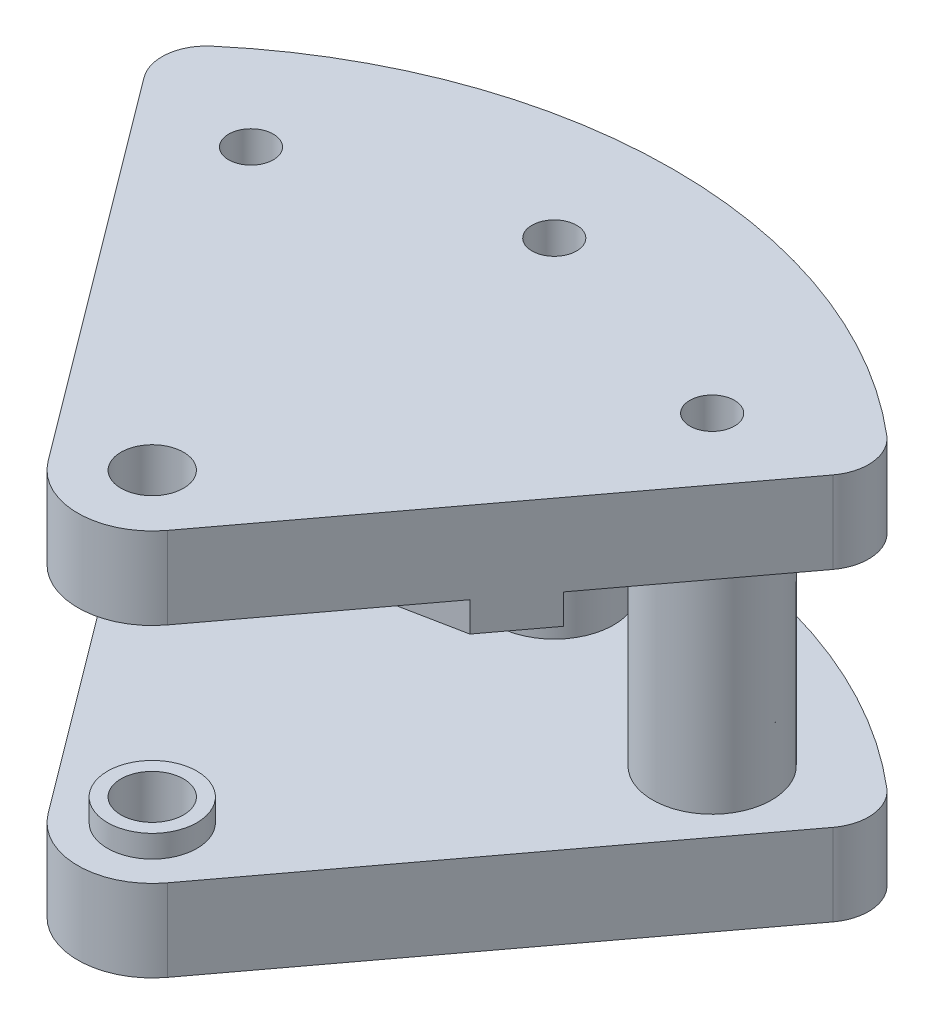
SolidWorks part; units mm, degrees
ref_plane "正面" through (0, 0, 0) normal (0, 0, 1) x (1, 0, 0)
ref_plane "平面" through (0, 0, 0) normal (0, 1, 0) x (1, 0, 0)
ref_plane "右側面" through (0, 0, 0) normal (1, 0, 0) x (0, 0, -1)
sketch "ｽｹｯﾁ1" plane through (0, 0, 0) normal (0, 1, 0) x (1, 0, 0)
  line L0 (-23.1297, 22.5835) -> (-4.0043, -2.9942)
  line L1 (23.1297, 22.5835) -> (4.0043, -2.9942)
  line L2 (-24.7487, 24.7487) -> (0, 0) construction
  line L3 (0, 0) -> (24.7487, 24.7487) construction
  line L4 (0, 0) -> (0, 35) construction
  line L5 (0, 0) -> (15.4866, 22.1171) construction
  line L6 (0, 0) -> (-15.4866, 22.1171) construction
  circle A0 centre (0, 0) radius 2.1
  arc A1 (22.6703, 26.6657) -> (-22.6703, 26.6657) centre (0, 0) ccw
  arc A2 (-4.0043, -2.9942) -> (4.0043, -2.9942) centre (0, 0) ccw
  arc A3 (22.6703, 26.6657) -> (23.1297, 22.5835) centre (20.7271, 24.38) cw
  arc A4 (-22.6703, 26.6657) -> (-23.1297, 22.5835) centre (-20.7271, 24.38) ccw
  arc A5 (15.4866, 22.1171) -> (-15.4866, 22.1171) centre (0, 0) ccw construction
  circle A6 centre (-15.4866, 22.1171) radius 1.5
  circle A7 centre (15.4866, 22.1171) radius 1.5
  circle A8 centre (-15.4866, 22.1171) radius 4 construction
  circle A9 centre (15.4866, 22.1171) radius 4 construction
  circle A10 centre (0, 27) radius 1.5
  circle A11 centre (0, 27) radius 4 construction
  point P3 (0, 35)
  dimension "D2" = 5
  dimension "D3" = 4.2
  dimension "D5" = 3
  dimension "D6" = 8
  dimension "D7" = 3
  dimension "D9" = 8
  dimension "D1" = 90
  dimension "D4" = 35
  dimension "D8" = 70
extrude "ﾎﾞｽ - 押し出し1" add sketch "ｽｹｯﾁ1" along normal blind 5.5
sketch "ｽｹｯﾁ2" plane through (0, 5.5, 0) normal (0, 1, 0) x (1, 0, 0)
  circle A0 centre (0, 27) radius 3
  circle A1 centre (15.4866, 22.1171) radius 3
  circle A2 centre (-15.4866, 22.1171) radius 3
  circle A4 centre (-15.4866, 22.1171) radius 1.5 construction
  circle A5 centre (0, 27) radius 1.5 construction
  circle A6 centre (-15.4866, 22.1171) radius 1.5
  circle A7 centre (0, 27) radius 1.5
  circle A8 centre (15.4866, 22.1171) radius 1.5 construction
  circle A9 centre (15.4866, 22.1171) radius 1.5
  dimension "D1" = 6
extrude "ﾎﾞｽ - 押し出し2" add sketch "ｽｹｯﾁ2" along normal blind 15 separate body
sketch "ｽｹｯﾁ3" plane through (0, 5.5, 0) normal (0, 1, 0) x (1, 0, 0)
  line L0 (0, 0) -> (-15.4866, 22.1171) construction
  line L1 (0, 0) -> (0, 27) construction
  circle A0 centre (-15.4866, 22.1171) radius 3.1
  circle A1 centre (-15.4866, 22.1171) radius 4
  circle A2 centre (0, 27) radius 3.1
  circle A3 centre (0, 27) radius 4
  circle A4 centre (15.4866, 22.1171) radius 3.1
  circle A5 centre (15.4866, 22.1171) radius 4
  dimension "D1" = 6.2
  dimension "D2" = 8
  dimension "D3" = 3
extrude "ﾎﾞｽ - 押し出し3" add sketch "ｽｹｯﾁ3" along normal blind 14.5 separate body
extrude "ﾎﾞｽ - 押し出し4" add sketch "ｽｹｯﾁ1<2>" along normal blind 5.5 from surface starting at face at (0, 20.5, -24)
sketch "ｽｹｯﾁ1<2>" plane through (0, 0, 0) normal (0, 1, 0) x (1, 0, 0) same geometry as "ｽｹｯﾁ1"
sketch "ｽｹｯﾁ4" plane through (0, 5.5, 0) normal (0, 1, 0) x (1, 0, 0)
  circle A0 centre (0, 0) radius 3
  circle A1 centre (0, 0) radius 2.1 construction
  circle A2 centre (0, 0) radius 2.1
  dimension "D1" = 6
extrude "ﾎﾞｽ - 押し出し5" add sketch "ｽｹｯﾁ4" along normal blind 1.5
ref_plane "平面1" through (0, 13, 0) normal (0, 1, 0) x (1, 0, 0)
sketch "ｽｹｯﾁ5" plane through (0, 20.5, 0) normal (0, -1, 0) x (-1, 0, 0)
  line L0 (-12.6994, 8.6344) -> (9.4205, 4.2492)
  line L1 (-23.1297, 22.5835) -> (-4.0043, -2.9942) construction
  line L2 (4.0043, -2.9942) -> (23.1297, 22.5835) construction
  line L3 (-15.3843, 12.225) -> (11.4121, 6.9128)
  line L4 (11.4121, 6.9128) -> (9.4205, 4.2492)
  line L6 (-15.3843, 12.225) -> (-12.6994, 8.6344)
  dimension "D1" = 42
  dimension "D2" = 6
  dimension "D3" = 3
extrude "ﾎﾞｽ - 押し出し6" add sketch "ｽｹｯﾁ5" along normal blind 2
